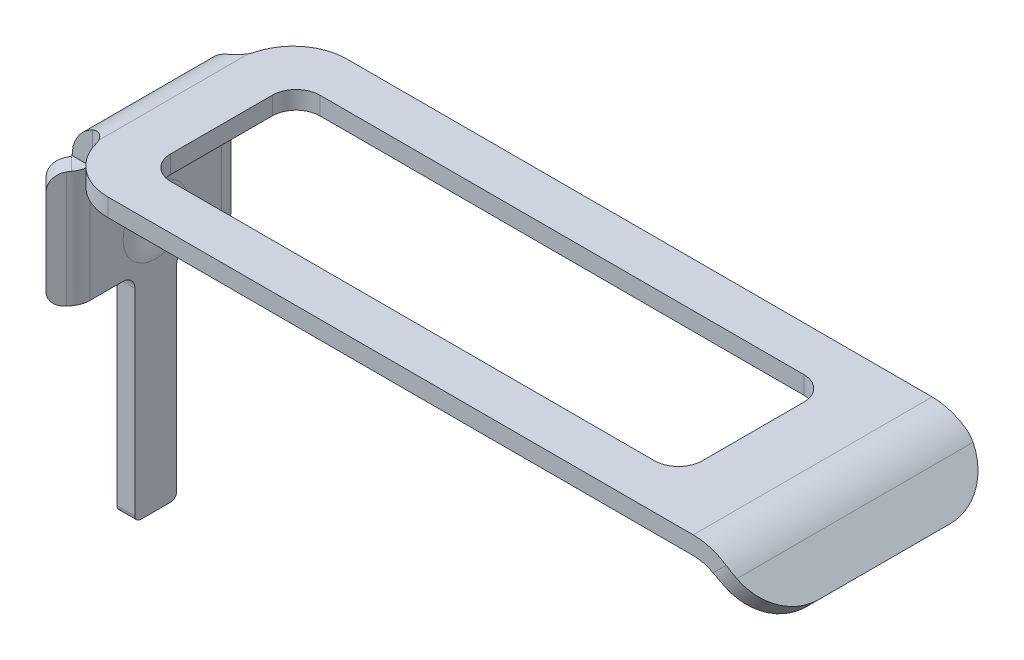
SolidWorks part; units mm, degrees
ref_plane "Спереди" through (0, 0, 0) normal (0, 0, 1) x (1, 0, 0)
ref_plane "Сверху" through (0, 0, 0) normal (0, 1, 0) x (1, 0, 0)
ref_plane "Справа" through (0, 0, 0) normal (1, 0, 0) x (0, 0, -1)
sketch "Sketch1" plane through (0, 0, 0) normal (0, 0, 1) x (1, 0, 0)
  line L0 (-0.3672, -8.4515) -> (-0.0672, -8.4515)
  line L1 (-0.0672, -8.4515) -> (-0.0672, -2.9015)
  line L2 (-0.3672, -8.4515) -> (-0.3672, -2.9015)
  line L3 (0.2328, -2.3015) -> (10.9307, -2.3015)
  line L4 (0.2328, -2.6015) -> (10.9307, -2.6015)
  line L5 (11.4257, -2.8065) -> (11.9206, -3.3015)
  line L6 (11.6378, -2.5944) -> (12.1328, -3.0894)
  line L7 (12.1328, -3.0894) -> (11.9206, -3.3015)
  line L8 (10.9307, -2.6015) -> (10.9307, -2.3015) construction
  arc A0 (10.9307, -2.3015) -> (11.6378, -2.5944) centre (10.9307, -3.3015) cw
  arc A1 (10.9307, -2.6015) -> (11.4257, -2.8065) centre (10.9307, -3.3015) cw
  arc A2 (0.2328, -2.6015) -> (-0.0672, -2.9015) centre (0.2328, -2.9015) ccw
  arc A3 (-0.3672, -2.9015) -> (0.2328, -2.3015) centre (0.2328, -2.9015) cw
  dimension "D4" = 1
  dimension "D5" = 1
  dimension "D6" = 0.6
  dimension "D7" = 0.3
  dimension "D1" = 0.3
  dimension "D2" = 0.3
  dimension "D3" = 6.15
  dimension "D8" = 45
  dimension "D9" = 12.5
extrude "Boss-Extrude1" add sketch "Sketch1" along normal mid plane 4
sketch "Sketch2" plane through (0, -2.3015, 0) normal (0, 1, 0) x (1, 0, 0)
  line L0 (0, 0) -> (1.0328, 0) construction
  line L1 (1.0328, 1.25) -> (9.9328, 1.25)
  line L2 (1.0328, 1.25) -> (1.0328, -1.25)
  line L3 (1.0328, -1.25) -> (9.9328, -1.25)
  line L4 (9.9328, 1.25) -> (9.9328, -1.25)
  line L5 (-0.3672, -2) -> (-0.3672, 2) construction
  dimension "D1" = 2.5
  dimension "D2" = 8.9
  dimension "D3" = 1.4
extrude "Cut-Extrude1" cut sketch "Sketch2" against normal through all
fillet "Fillet1" radius 0.9 2 edges at (12.0267, -3.1954, -2) (12.0267, -3.1954, 2)
sketch "Sketch3" plane through (-0.3672, 0, 0) normal (-1, 0, 0) x (0, 0, 1)
  line L0 (-0.35, -8.4515) -> (-0.35, -4.8515)
  line L1 (2, -8.4515) -> (-2, -8.4515) construction
  line L2 (-0.35, -4.8515) -> (-2, -4.8515)
  line L3 (-2, -8.4515) -> (-2, -2.9015) construction
  line L4 (-2, -4.8515) -> (-2, -8.4515)
  line L5 (-2, -8.4515) -> (-0.35, -8.4515)
  line L6 (0.35, -4.8515) -> (2, -4.8515)
  line L7 (2, -8.4515) -> (2, -2.9015) construction
  line L8 (2, -4.8515) -> (2, -8.4515)
  line L9 (2, -8.4515) -> (0.35, -8.4515)
  line L10 (0.35, -8.4515) -> (0.35, -4.8515)
  line L11 (0.35, -4.8515) -> (-0.35, -4.8515) construction
  line L12 (0, -4.8515) -> (0, -8.4515) construction
  dimension "D1" = 3.6
  dimension "D2" = 0.7
extrude "Cut-Extrude2" cut sketch "Sketch3" against normal through all
sketch "Sketch4" plane through (0, 0, -2) normal (0, 0, -1) x (-1, 0, 0)
  line L0 (-10.9307, -2.3015) -> (-0.2328, -2.3015) construction
  line L1 (0.3672, -4.8515) -> (0.0672, -4.8515)
  line L2 (0.3672, -4.8515) -> (0.3672, -2.3015)
  line L3 (0.3672, -2.3015) -> (0.0672, -2.3015)
  line L4 (0.0672, -4.8515) -> (0.0672, -2.9015)
  line L5 (0.0672, -4.8515) -> (0.0672, -2.9015) construction
  line L7 (-0.2328, -2.6015) -> (-10.9307, -2.6015) construction
  line L8 (-0.2328, -2.6015) -> (-0.2328, -2.3015)
  line L9 (-0.2328, -2.3015) -> (0.0672, -2.3015)
  arc A0 (-0.2328, -2.6015) -> (0.0672, -2.9015) centre (-0.2328, -2.9015) cw
extrude "Cut-Extrude3" cut sketch "Sketch4" against normal blind 0.9
sketch "Sketch5" plane through (0, 0, 2) normal (0, 0, 1) x (1, 0, 0)
  line L0 (0.2328, -2.6015) -> (0.2328, -2.3015)
  line L1 (-0.3672, -4.8515) -> (-0.0672, -4.8515)
  line L2 (-0.3672, -4.8515) -> (-0.3672, -2.9015)
  line L4 (-0.0672, -4.8515) -> (-0.0672, -2.9015)
  line L5 (0.2328, -2.3015) -> (-0.3672, -2.3015)
  line L6 (-0.3672, -2.3015) -> (-0.3672, -2.9015)
  arc A0 (-0.0672, -2.9015) -> (0.2328, -2.6015) centre (0.2328, -2.9015) cw
extrude "Cut-Extrude4" cut sketch "Sketch5" against normal blind 0.9
fillet "Fillet2" radius 0.9 2 edges at (0.2328, -2.4515, -2) (0.2328, -2.4515, 2)
sketch "Sketch6" plane through (0, -4.8515, 0) normal (0, -1, 0) x (1, 0, 0)
  line L0 (-0.1819, 1.3768) -> (-0.3551, 1.55)
  line L1 (-0.3551, 1.55) -> (-0.5672, 1.3379)
  line L2 (-0.5672, 1.3379) -> (-0.394, 1.1646)
  line L3 (-0.3672, -1.1) -> (-0.0672, -1.1)
  line L4 (-0.0672, -0.35) -> (-0.0672, -1.1) construction
  line L5 (-0.1819, -1.3768) -> (-0.3551, -1.55)
  line L6 (-0.3551, -1.55) -> (-0.5672, -1.3379)
  line L7 (-0.5672, -1.3379) -> (-0.394, -1.1646)
  line L8 (-0.3672, -0.35) -> (-0.3672, -1.1) construction
  line L9 (-0.3672, 1.1) -> (-0.3672, 0.35) construction
  line L10 (-0.0672, 1.1) -> (-0.0672, -1.1) construction
  line L11 (-0.3672, 0) -> (-1.6427, 0) construction
  line L12 (-0.3672, 0.35) -> (-0.3672, -0.35) construction
  line L13 (-0.4586, 1.1) -> (-0.0672, 1.1)
  line L14 (-0.0672, 1.1) -> (-0.0672, 0.35) construction
  arc A0 (-0.394, -1.1646) -> (-0.3672, -1.1) centre (-0.4586, -1.1) ccw
  arc A1 (-0.394, 1.1646) -> (-0.3672, 1.1) centre (-0.4586, 1.1) cw
  arc A2 (-0.1819, 1.3768) -> (-0.0672, 1.1) centre (-0.4586, 1.1) cw
  arc A3 (-0.1819, -1.3768) -> (-0.0672, -1.1) centre (-0.4586, -1.1) ccw
  line M2 (-0.3672, -1.1) -> (-0.0672, -1.1)
  dimension "D1" = 3.1
  dimension "D3" = 45
  dimension "D4" = 45
  dimension "D5" = 0.5
extrude "Boss-Extrude2" add sketch "Sketch6" against normal up to vertex (1.95 mm away) contours L5 A3 A0 L7 L6 M2 | A2 L0 L1 L2 A1 L13 region at (-0.3042, -4.8515, 1.2894) region at (-0.3042, -4.8515, -1.2894) up to point (-0.3672, -2.9015, -1.1)
fillet "Fillet3" radius 0.4 4 edges at (9.9328, -2.4515, -1.25) (1.0328, -2.4515, -1.25) (1.0328, -2.4515, 1.25) (9.9328, -2.4515, 1.25)
fillet "Fillet5" radius 0.3 2 edges at (-0.4612, -2.9015, 1.4439) (-0.4612, -2.9015, -1.4439)
fillet "Fillet6" radius 0.3 2 edges at (0.2328, -2.4515, 1.1) (0.2328, -2.4515, -1.1)
fillet "Fillet7" radius 0.2 2 edges at (-0.2172, -4.8515, 0.35) (-0.2172, -4.8515, -0.35)
fillet "Fillet8" radius 0.1 2 edges at (-0.2172, -8.4515, 0.35) (-0.2172, -8.4515, -0.35)
fillet "Fillet9" radius 0.2 2 edges at (-0.4612, -4.8515, 1.4439) (-0.4612, -4.8515, -1.4439)
sketch "Sketch7" plane through (0, 0, 0) normal (0, 0, 1) x (1, 0, 0)
  line L0 (-0.3672, -2.3669) -> (-0.3672, -8.4515) construction
  line L1 (-0.3672, -8.3515) -> (-0.3672, -5.0515) construction
  line L2 (-0.6172, -4.2515) -> (-0.0172, -4.2515) construction
  line L3 (-0.0672, -8.3515) -> (-0.0672, -5.0515) construction
  line L5 (-0.4258, -4.8515) -> (-0.2137, -4.8515) construction
  line L6 (-0.3672, -3.6515) -> (-0.3672, -4.8515)
  line L7 (-0.6172, -4.2515) -> (-0.3672, -4.2515)
  arc A0 (-0.4397, -3.8255) -> (-0.4397, -4.6775) centre (-0.0172, -4.2515) ccw
  arc A1 (-0.4397, -4.6775) -> (-0.3672, -4.8515) centre (-0.6122, -4.8515) cw
  arc A2 (-0.4397, -3.8255) -> (-0.3672, -3.6515) centre (-0.6122, -3.6515) ccw
  dimension "D2" = 0.6
  dimension "D1" = 0.55
  dimension "D3" = 1.2
revolve "Revolve2" add sketch "Sketch7" angle 360 about L7 region at (-0.4677, -4.0567, 0)
sketch "Sketch9" plane through (0, 0, 0) normal (0, 0, 1) x (1, 0, 0)
  line L0 (-0.0672, -3.7055) -> (-0.0672, -4.7976)
  line L1 (-0.3172, -4.2515) -> (-0.6172, -4.2515) construction
  line L2 (-0.0672, -8.3515) -> (-0.0672, -5.0515) construction
  line L3 (-0.3172, -4.2515) -> (-0.0672, -4.2515)
  arc A0 (-0.2132, -4.0244) -> (-0.2132, -4.4786) centre (-0.0172, -4.2515) ccw
  arc A1 (-0.2132, -4.4786) -> (-0.0672, -4.7976) centre (-0.4886, -4.7976) cw
  arc A2 (-0.2132, -4.0244) -> (-0.0672, -3.7055) centre (-0.4886, -3.7055) ccw
  arc A4 (-0.4397, -3.8255) -> (-0.4397, -4.6775) centre (-0.0172, -4.2515) ccw construction
  dimension "D2" = 0.3
  dimension "D1" = 0.3
revolve "Cut-Revolve1" cut sketch "Sketch9" angle 360 about L3 region at (-0.1629, -4.1021, 0)
equation "\"D2@Sketch1\"=\"D1@Sketch1\""
equation "\"D6@Sketch1\"=\"D2@Sketch1\"*2"
equation "\"D7@Sketch1\"=\"D2@Sketch1\""
equation "\"D1@Cut-Extrude4\"=0.6"
equation "\"D4@Sketch6\"=\"D3@Sketch6\""
